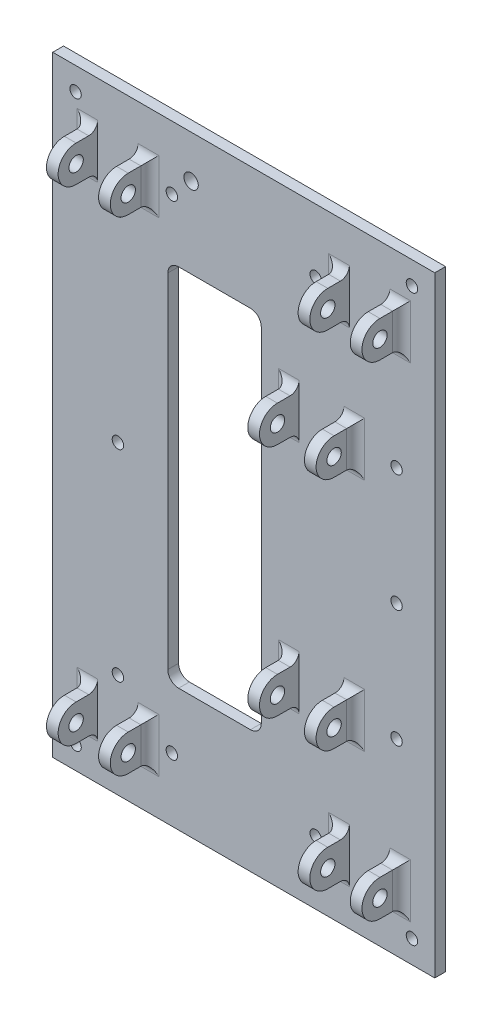
SolidWorks part; units mm, degrees
other "Markup3"
sketch "Sketch7" plane through (228.6, -342.9, 31.75) normal (0.076, -0.0024, 0.9971) x (0.9961, 0.0458, -0.0758)
other "Markup4"
sketch "Sketch8" plane through (228.6, -342.9, 31.75) normal (0.076, -0.0024, 0.9971) x (0.9961, 0.0458, -0.0758)
material "7075-T6 (SN)"
ref_plane "Front Plane" through (0, 0, 0) normal (0, 0, 1) x (1, 0, 0)
ref_plane "Top Plane" through (0, 0, 0) normal (0, 1, 0) x (1, 0, 0)
ref_plane "Right Plane" through (0, 0, 0) normal (1, 0, 0) x (0, 0, -1)
sketch "Sketch1" plane through (0, 0, 0) normal (0, 0, 1) x (1, 0, 0)
  line L1 (0, 0) -> (212.5, 0)
  line L2 (0, 0) -> (0, -339.725)
  line L3 (0, -339.725) -> (212.5, -339.725)
  line L4 (212.5, 0) -> (212.5, -339.725)
  dimension "D1" = 339.725
  dimension "D2" = 212.5
extrude "Boss-Extrude1" add sketch "Sketch1" along normal blind 6
sketch "Sketch2" plane through (0, 0, 6) normal (0, 0, 1) x (1, 0, 0)
  line L0 (0, 0) -> (0, -339.725) construction
  line L1 (25, -25.2425) -> (47.5, -25.2425) construction
  line L2 (25, -25.2425) -> (25, -45.2425)
  line L3 (25, -45.2425) -> (47.5, -45.2425) construction
  line L4 (47.5, -25.2425) -> (47.5, -45.2425)
  line L5 (165, -25.2425) -> (187.5, -25.2425) construction
  line L6 (165, -25.2425) -> (165, -45.2425)
  line L7 (165, -45.2425) -> (187.5, -45.2425) construction
  line L8 (187.5, -25.2425) -> (187.5, -45.2425)
  line L18 (137, -114.5325) -> (137, -225.1925) construction
  line L19 (0, -169.8625) -> (106.25, -169.8625) construction
  line L20 (54, -35.2425) -> (158.5, -35.2425) construction
  line L26 (165, -25.2425) -> (158.5, -25.2425)
  line L27 (165, -25.2425) -> (165, -45.2425)
  line L28 (165, -45.2425) -> (158.5, -45.2425)
  line L29 (158.5, -25.2425) -> (158.5, -45.2425)
  line L30 (187.5, -25.2425) -> (194, -25.2425)
  line L31 (187.5, -25.2425) -> (187.5, -45.2425)
  line L32 (187.5, -45.2425) -> (194, -45.2425)
  line L33 (194, -25.2425) -> (194, -45.2425)
  line L34 (47.5, -25.2425) -> (54, -25.2425)
  line L35 (47.5, -25.2425) -> (47.5, -45.2425)
  line L36 (47.5, -45.2425) -> (54, -45.2425)
  line L37 (54, -25.2425) -> (54, -45.2425)
  line L38 (25, -25.2425) -> (18.5, -25.2425)
  line L39 (25, -25.2425) -> (25, -45.2425)
  line L40 (25, -45.2425) -> (18.5, -45.2425)
  line L41 (18.5, -25.2425) -> (18.5, -45.2425)
  line L65 (212.5, -339.725) -> (212.5, 0) construction
  line L66 (137, -225.1925) -> (162, -225.1925) construction
  line L67 (158.5, -304.4825) -> (194, -304.4825) construction
  line L68 (149.5, -104.5325) -> (149.5, -235.1925) construction
  line L76 (18.5, -35.2425) -> (54, -35.2425) construction
  line L77 (18.5, -304.4825) -> (54, -304.4825) construction
  line L78 (36.25, -35.2425) -> (36.25, -304.4825) construction
  line L79 (137, -94.5325) -> (162, -94.5325) construction
  line L80 (54, -304.4825) -> (158.5, -304.4825) construction
  line L81 (106.25, -35.2425) -> (106.25, -304.4825) construction
  line L82 (106.25, -169.8625) -> (212.5, -169.8625) construction
  line L83 (130.5, -94.5325) -> (130.5, -114.5325)
  line L84 (137, -114.5325) -> (130.5, -114.5325)
  line L86 (137, -94.5325) -> (130.5, -94.5325)
  line L88 (137, -94.5325) -> (137, -114.5325)
  line L89 (162, -114.5325) -> (168.5, -114.5325)
  line L90 (162, -114.5325) -> (162, -94.5325)
  line L91 (168.5, -94.5325) -> (168.5, -114.5325)
  line L92 (162, -94.5325) -> (168.5, -94.5325)
  line L93 (130.5, -235.1925) -> (168.5, -235.1925) construction
  line L96 (137, -245.1925) -> (162, -245.1925) construction
  line L97 (162, -245.1925) -> (168.5, -245.1925)
  line L98 (168.5, -245.1925) -> (168.5, -225.1925)
  line L103 (130.5, -104.5325) -> (168.5, -104.5325) construction
  line L104 (137, -114.5325) -> (162, -114.5325) construction
  line L106 (158.5, -35.2425) -> (194, -35.2425) construction
  line L108 (176.25, -35.2425) -> (176.25, -304.4825) construction
  line L109 (165, -294.4825) -> (187.5, -294.4825) construction
  line L112 (165, -314.4825) -> (187.5, -314.4825) construction
  line L113 (25, -294.4825) -> (47.5, -294.4825) construction
  line L114 (25, -314.4825) -> (47.5, -314.4825) construction
  line L117 (162, -114.5325) -> (162, -225.1925) construction
  line L118 (18.5, -314.4825) -> (18.5, -294.4825)
  line L119 (25, -294.4825) -> (18.5, -294.4825)
  line L120 (25, -314.4825) -> (25, -294.4825)
  line L121 (25, -314.4825) -> (18.5, -314.4825)
  line L122 (54, -314.4825) -> (54, -294.4825)
  line L123 (47.5, -294.4825) -> (54, -294.4825)
  line L124 (47.5, -314.4825) -> (47.5, -294.4825)
  line L125 (47.5, -314.4825) -> (54, -314.4825)
  line L126 (194, -314.4825) -> (194, -294.4825)
  line L127 (187.5, -294.4825) -> (194, -294.4825)
  line L128 (187.5, -314.4825) -> (187.5, -294.4825)
  line L129 (187.5, -314.4825) -> (194, -314.4825)
  line L130 (158.5, -314.4825) -> (158.5, -294.4825)
  line L131 (165, -294.4825) -> (158.5, -294.4825)
  line L132 (165, -314.4825) -> (165, -294.4825)
  line L133 (165, -314.4825) -> (158.5, -314.4825)
  line L134 (187.5, -314.4825) -> (187.5, -294.4825)
  line L135 (165, -314.4825) -> (165, -294.4825)
  line L136 (47.5, -314.4825) -> (47.5, -294.4825)
  line L137 (25, -314.4825) -> (25, -294.4825)
  line L138 (162, -225.1925) -> (162, -245.1925)
  line L139 (162, -225.1925) -> (168.5, -225.1925)
  line L140 (137, -245.1925) -> (137, -225.1925)
  line L141 (137, -245.1925) -> (130.5, -245.1925)
  line L142 (137, -225.1925) -> (130.5, -225.1925)
  line L143 (130.5, -245.1925) -> (130.5, -225.1925)
  point P63 (194, -35.2425)
  point P101 (212.5, -169.8625)
  point P103 (158.5, -35.2425)
  dimension "D5" = 43.25
  dimension "D1" = 20
  dimension "D2" = 22.5
  dimension "D3" = 6.5
  dimension "D4" = 199.95
  dimension "D6" = 134.62
  dimension "D7" = 134.62
  dimension "D8" = 25
  dimension "D9" = 70
  dimension "D10" = 25
extrude "Boss-Extrude2" add sketch "Sketch2" along normal blind 24 contours L133 L132 L131 L130 | L128 L129 L126 L127 | L139 L138 L97 L98 | L143 L141 L140 L142 | L124 L125 L122 L123 | L121 L120 L119 L118 | L92 L90 L89 L91 | L88 L86 L83 L84 | L33 L30 L8 L32 | L37 L34 L4 L36 | L38 L41 L40 L2 | L26 L29 L28 L27 region at (21.75, -35.2425, 6) region at (50.75, -35.2425, 6) region at (190.75, -35.2425, 6) region at (133.75, -104.5325, 6) region at (165.25, -104.5325, 6) region at (165.25, -235.1925, 6) region at (21.75, -304.4825, 6) region at (50.75, -304.4825, 6) region at (190.75, -304.4825, 6) region at (161.75, -304.4825, 6) region at (133.75, -235.1925, 6)
sketch "Sketch3" plane through (18.5, 0, 0) normal (-1, 0, 0) x (0, 0, 1)
  line L0 (18, -104.5325) -> (6, -104.5325) construction
  line L1 (18, -304.4825) -> (6, -304.4825) construction
  line L2 (22, -235.1925) -> (37.7332, -235.1925) construction
  line L3 (22, -235.1925) -> (6, -235.1925) construction
  line L4 (18, -35.2425) -> (6, -35.2425) construction
  line L5 (6, -25.2425) -> (6, -45.2425) construction
  line L6 (6, -245.1925) -> (6, -225.1925) construction
  line L7 (6, 0) -> (6, -339.725) construction
  line L9 (18, -25.2425) -> (18, -12.9829)
  line L10 (18, -12.9829) -> (51.9495, -12.9829)
  line L11 (6, -245.1925) -> (6, -225.1925) construction
  line L12 (51.9495, -12.9829) -> (51.9495, -57.481)
  line L13 (51.9495, -57.481) -> (18, -57.481)
  line L14 (18, -57.481) -> (18, -45.2425)
  line L15 (52.4423, -132.3991) -> (18, -132.3991)
  line L16 (18, -94.5325) -> (18, -71.5915)
  line L17 (18, -71.5915) -> (52.4423, -71.5915)
  line L18 (18, -132.3991) -> (18, -114.5325)
  line L19 (52.4423, -71.5915) -> (52.4423, -132.3991)
  line L20 (52.5995, -270.3754) -> (18, -270.3754)
  line L21 (18, -225.1925) -> (18, -207.3064)
  line L22 (18, -207.3064) -> (52.5995, -207.3064)
  line L23 (18, -270.3754) -> (18, -245.1925)
  line L24 (52.5995, -207.3064) -> (52.5995, -270.3754)
  line L25 (52.621, -326.7211) -> (18, -326.7211)
  line L26 (18, -294.4825) -> (18, -282.2228)
  line L27 (18, -282.2228) -> (52.621, -282.2228)
  line L28 (18, -326.7211) -> (18, -314.4825)
  line L29 (52.621, -282.2228) -> (52.621, -326.7211)
  line L30 (6, -94.5325) -> (6, -114.5325) construction
  line L31 (30, -25.2425) -> (6, -25.2425) construction
  line L32 (30, -94.5325) -> (6, -94.5325) construction
  line L35 (6, -314.4825) -> (6, -294.4825) construction
  line L36 (6, -314.4825) -> (6, -294.4825) construction
  line L37 (18, -35.2425) -> (18, -104.5325) construction
  line L38 (18, -104.5325) -> (18, -235.1925) construction
  line L39 (18, -235.1925) -> (18, -304.4825) construction
  line L41 (30, -225.1925) -> (6, -225.1925) construction
  circle A0 centre (18, -35.2425) radius 4
  circle A1 centre (18, -235.1925) radius 4
  circle A2 centre (18, -35.2425) radius 5.5 construction
  circle A3 centre (18, -304.4825) radius 4
  circle A4 centre (18, -104.5325) radius 4
  arc A5 (18, -45.2425) -> (18, -25.2425) centre (18, -35.2425) ccw
  arc A6 (18, -114.5325) -> (18, -94.5325) centre (18, -104.5325) ccw
  arc A7 (18, -245.1925) -> (18, -225.1925) centre (18, -235.1925) ccw
  arc A8 (18, -314.4825) -> (18, -294.4825) centre (18, -304.4825) ccw
  point P62 (6, -304.4825)
  point P67 (6, -235.1925)
  dimension "D1" = 8
  dimension "D2" = 8
  dimension "D4" = 11
  dimension "D3" = 12
extrude "Cut-Extrude1" cut sketch "Sketch3" against normal through all both and the other way through all
fillet "Fillet2" radius 5 36 edges at (158.5, -304.4825, 6) (18.5, -304.4825, 6) (21.75, -45.2425, 6) (18.5, -35.2425, 6) (21.75, -25.2425, 6) (50.75, -25.2425, 6) (50.75, -45.2425, 6) (54, -35.2425, 6) (161.75, -25.2425, 6) (190.75, -25.2425, 6) (194, -35.2425, 6) (190.75, -45.2425, 6) (161.75, -45.2425, 6) (158.5, -35.2425, 6) (168.5, -104.5325, 6) (165.25, -114.5325, 6) (133.75, -114.5325, 6) (130.5, -104.5325, 6) (165.25, -94.5325, 6) (133.75, -94.5325, 6) (21.75, -294.4825, 6) (50.75, -294.4825, 6) (54, -304.4825, 6) (194, -304.4825, 6) (161.75, -294.4825, 6) (190.75, -294.4825, 6) (190.75, -314.4825, 6) (161.75, -314.4825, 6) (50.75, -314.4825, 6) (21.75, -314.4825, 6) (165.25, -225.1925, 6) (133.75, -225.1925, 6) (130.5, -235.1925, 6) (133.75, -245.1925, 6) (165.25, -245.1925, 6) (168.5, -235.1925, 6)
sketch "Sketch5" plane through (0, 0, 6) normal (0, 0, 1) x (1, 0, 0)
  line L0 (212.5, 0) -> (0, 0) construction
  line L1 (0, 0) -> (0, -339.725) construction
  line L2 (212.5, -339.725) -> (212.5, 0) construction
  line L5 (0, -169.8625) -> (212.5, -169.8625) construction
  line L6 (153.5, -35.2425) -> (59, -35.2425) construction
  line L7 (59, -20.2425) -> (59, -50.2425) construction
  line L8 (191.25, -104.5325) -> (191.25, -169.8625) construction
  line L9 (13.5, -50.2425) -> (59, -50.2425) construction
  line L10 (25, -50.2425) -> (13.5, -50.2425) construction
  line L11 (36.25, -50.2425) -> (36.25, -169.8625) construction
  line L12 (191.25, -169.8625) -> (191.25, -235.1925) construction
  line L15 (173.5, -89.5325) -> (173.5, -119.5325) construction
  line L16 (106.25, 0) -> (106.25, -339.725) construction
  line L17 (173.5, -104.5325) -> (191.25, -104.5325) construction
  line L26 (0, -339.725) -> (212.5, -339.725) construction
  circle A0 centre (12.7, -12.7) radius 3.175
  circle A1 centre (199.8, -12.7) radius 3.175
  circle A2 centre (66.25, -35.2425) radius 3.175
  circle A3 centre (146.25, -35.2425) radius 3.175
  circle A4 centre (176.25, -57.8625) radius 3.175
  circle A5 centre (36.25, -57.8625) radius 3.175
  circle A6 centre (191.25, -104.5325) radius 3.175
  circle A7 centre (36.25, -169.8625) radius 3.175
  circle A8 centre (191.25, -169.8625) radius 3.175
  circle A9 centre (36.25, -281.8625) radius 3.175
  circle A10 centre (66.25, -304.4825) radius 3.175
  circle A11 centre (12.7, -327.025) radius 3.175
  circle A12 centre (199.8, -327.025) radius 3.175
  circle A13 centre (146.25, -304.4825) radius 3.175
  circle A15 centre (191.25, -235.1925) radius 3.175
  dimension "D1" = 93.55
  dimension "D3" = 40
  dimension "D5" = 85
  dimension "D8" = 6.35
  dimension "D2" = 157.1625
  dimension "D4" = 112
extrude "Cut-Extrude2" cut sketch "Sketch5" against normal through all contours A0 | A5 | A3 | A1 | A4 | A6 | A7 | A8 | A12 | A13 | A10 | A9 | A11 | A15 | A2 region at (12.7, -12.7, 6) region at (199.8, -12.7, 6) region at (146.25, -35.2425, 6) region at (176.25, -57.8625, 6) region at (36.25, -57.8625, 6) region at (191.25, -104.5325, 6) region at (36.25, -169.8625, 6) region at (191.25, -169.8625, 6) region at (36.25, -281.8625, 6) region at (66.25, -304.4825, 6) region at (12.7, -327.025, 6) region at (199.8, -327.025, 6) region at (146.25, -304.4825, 6)
sketch "Sketch9" plane through (0, 0, 6) normal (0, 0, 1) x (1, 0, 0)
  line L0 (0, -169.8625) -> (212.5, -169.8625) construction
  line L11 (0, 0) -> (0, -339.725) construction
  line L12 (212.5, -339.725) -> (212.5, 0) construction
  line L14 (70, -271.3625) -> (110, -271.3625)
  line L15 (64, -265.3625) -> (64, -74.3625)
  line L16 (70, -68.3625) -> (110, -68.3625)
  line L17 (116, -265.3625) -> (116, -74.3625)
  line L18 (64, -271.3625) -> (116, -68.3625) construction
  line L19 (64, -68.3625) -> (116, -271.3625) construction
  arc A0 (110, -271.3625) -> (116, -265.3625) centre (110, -265.3625) ccw
  arc A1 (70, -271.3625) -> (64, -265.3625) centre (70, -265.3625) cw
  arc A2 (64, -74.3625) -> (70, -68.3625) centre (70, -74.3625) cw
  arc A5 (110, -68.3625) -> (116, -74.3625) centre (110, -74.3625) cw
  point P6 (90, -169.8625)
  point P22 (169.7848, -178.533)
  point P23 (214.9568, -251.8775)
  point P24 (158.9712, -185.193)
  point P25 (204.1432, -258.5375)
  dimension "D1" = 90
  dimension "D3" = 52
  dimension "D4" = 6
  dimension "D2" = 203
extrude "Cut-Extrude3" cut sketch "Sketch9" against normal through all contours L15 A2 L16 A5 L17 A0 L14 A1
sketch3d "3DSketch1"
  line L0 (18.5, -35.2425, 18) -> (194, -35.2425, 18) construction
  line L1 (25, -35.2425, 18) -> (18.5, -35.2425, 18) construction
  line L2 (194, -35.2425, 18) -> (187.5, -35.2425, 18) construction
  line L3 (194, -35.2425, 18) -> (187.5, -35.2425, 18) construction
  line L5 (194, -304.4825, 18) -> (187.5, -304.4825, 18) construction
  line L6 (194, -304.4825, 18) -> (18.5, -304.4825, 18) construction
  line L7 (25, -304.4825, 18) -> (18.5, -304.4825, 18) construction
  circle A0 centre (194, -35.2425, 18) radius 4 construction
  point P17 (198, -35.2425, 18)
  point P18 (194, -35.2425, 18)
sketch "Sketch10" plane through (0, 0, 6) normal (0, 0, 1) x (1, 0, 0)
  circle A0 centre (180.4782, -317.5598) radius 4 construction
  circle A1 centre (180.4782, -317.5598) radius 4
extrude "Cut-Extrude4" cut sketch "Sketch10" against normal blind 18
sketch "Sketch11" plane through (0, 0, 6) normal (0, 0, 1) x (1, 0, 0)
  circle A0 centre (76.9625, -23.6135) radius 4 construction
  circle A1 centre (76.9625, -23.6135) radius 4
extrude "Cut-Extrude5" cut sketch "Sketch11" against normal blind 14.986
